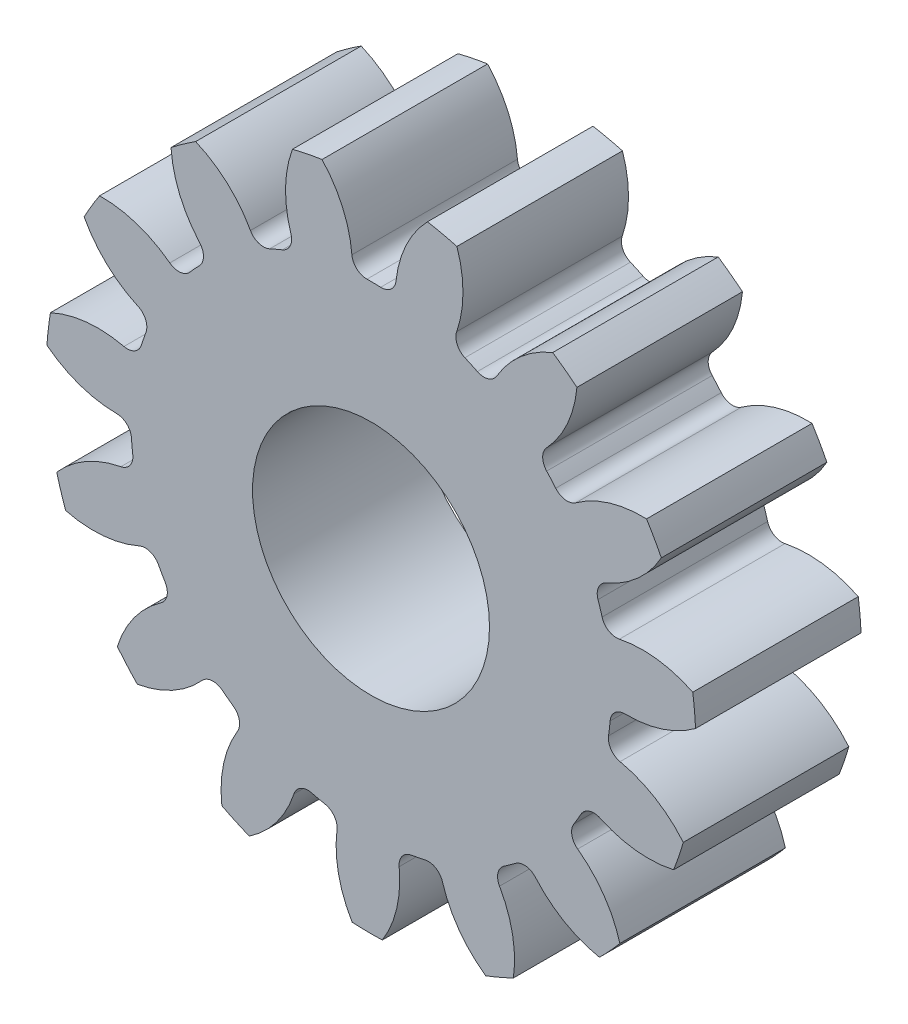
SolidWorks part; units mm, degrees
material "ABS"
ref_plane "Front" through (0, 0, 0) normal (0, 0, 1) x (1, 0, 0)
ref_plane "Top" through (0, 0, 0) normal (0, 1, 0) x (1, 0, 0)
ref_plane "Right" through (0, 0, 0) normal (1, 0, 0) x (0, 0, -1)
sketch "Sketch3" plane through (0, 0, 0) normal (0, 0, 1) x (1, 0, 0)
  circle A0 centre (0, 0) radius 21.59
  dimension "od" = 43.18
extrude "gearBody" add sketch "Sketch3" along normal blind 11
sketch "Sketch2" plane through (0, 0, 0) normal (0, 0, 1) x (1, 0, 0)
  line L0 (0, 0) -> (17.0393, 7.0579) construction
  line L1 (22.0105, -8.0941) -> (0, 0) construction
  line L2 (0, 0) -> (36.3143, 0) construction
  line L3 (19.0486, -0.229) -> (18.5878, -4.1711) construction
  line L5 (18.8182, -2.2) -> (0, 0) construction
  line L7 (0, 0) -> (18.4432, 0) construction
  arc A0 (18.4395, -0.3701) -> (18.0276, -3.8932) centre (0, 0) ccw construction
  arc A1 (21.5666, 1.0048) -> (20.7532, -5.9524) centre (0, 0) ccw construction
  arc A2 (19.0486, -0.229) -> (18.5878, -4.1711) centre (0, 0) ccw construction
  arc A3 (15.7838, -2.3046) -> (15.8898, -1.3984) centre (0, 0) ccw
  arc A4 (22.0105, -8.0941) -> (16.5506, -3.4102) centre (14.9518, -10.798) ccw
  arc A5 (22.0105, -8.0941) -> (23.2839, 2.7987) centre (0, 0) ccw
  arc A6 (23.2839, 2.7987) -> (16.8909, -0.4995) centre (17.0393, 7.0579) cw
  arc A7 (15.8898, -1.3984) -> (16.8909, -0.4995) centre (16.8715, -1.4848) cw
  arc A8 (16.5506, -3.4102) -> (15.7838, -2.3046) centre (16.759, -2.4469) cw
  point P6 (23.2839, 2.7987)
  point P22 (22.0105, -8.0941)
  dimension "baseDia" = 36.8864
  dimension "od" = 43.18
  dimension "pd" = 38.1
  dimension "rd" = 31.9024
  dimension "rFillet" = 0.9855
  dimension "pointX" = 23.2839
  dimension "pointY" = 2.7987
  dimension "CTT" = 3.9421
  dimension "flankCenterAngle" = 22.5
extrude "toothCut" cut sketch "Sketch2" along normal through all
pattern_circular "CirPattern1" count 15 over 360 about axis through (0, 0, 11) along (0, 0, -1) of "toothCut"
sketch "hub1Dia" plane through (0, 0, 0) normal (0, 0, -1) x (-1, 0, 0)
  circle A0 centre (0, 0) radius 12.7
  dimension "hub1Dia" = 25.4
sketch "hub2Dia" plane through (0, 0, 11) normal (0, 0, 1) x (1, 0, 0)
  circle A0 centre (0, 0) radius 12.7
  dimension "hub2dia" = 25.4
sketch "boreDia" plane through (0, 0, 0) normal (0, 0, 1) x (1, 0, 0)
  circle A0 centre (0, 0) radius 7.874
  dimension "boreDia" = 15.748
extrude "bore" cut sketch "boreDia" against normal mid plane 25400
